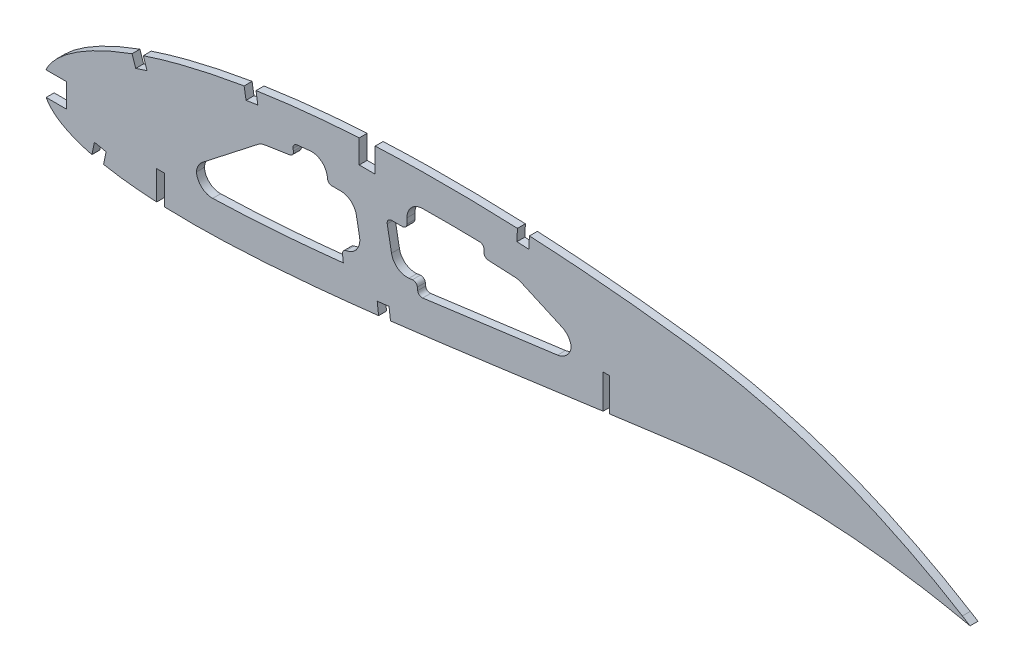
SolidWorks part; units mm, degrees
ref_plane "Front Plane" through (0, 0, 0) normal (0, 0, 1) x (1, 0, 0)
ref_plane "Top Plane" through (0, 0, 0) normal (0, 1, 0) x (1, 0, 0)
ref_plane "Right Plane" through (0, 0, 0) normal (1, 0, 0) x (0, 0, -1)
curve "Curve1"
  spline degree 3 poles (383.949, 0.5986, 0) (383.9196, 0.6168, 0) (383.802, 0.6894, 0) (383.5372, 0.8518, 0) (383.0962, 1.1224, 0) (382.4788, 1.4992, 0) (381.6856, 1.9812, 0) (380.716, 2.5651, 0) (379.5708, 3.249, 0) (378.2502, 4.0295, 0) (376.7543, 4.9032, 0) (375.0838, 5.8664, 0) (373.2387, 6.9137, 0) (371.2197, 8.0407, 0) (369.0276, 9.2423, 0) (366.6628, 10.5128, 0) (364.1261, 11.8459, 0) (361.4185, 13.2358, 0) (358.5405, 14.6749, 0) (355.4934, 16.1571, 0) (352.2782, 17.675, 0) (348.8962, 19.2207, 0) (345.3491, 20.7877, 0) (341.638, 22.3663, 0) (337.765, 23.9497, 0) (333.7318, 25.5289, 0) (329.5407, 27.0966, 0) (325.1933, 28.6428, 0) (320.6929, 30.1607, 0) (316.0417, 31.6403, 0) (311.2431, 33.0737, 0) (306.2997, 34.4516, 0) (301.2157, 35.767, 0) (295.9944, 37.0101, 0) (290.6401, 38.1728, 0) (285.1572, 39.2479, 0) (279.5502, 40.2249, 0) (273.8346, 41.1028, 0) (268.1025, 41.8331, 0) (262.3821, 42.5494, 0) (256.6703, 43.2222, 0) (250.8886, 43.8666, 0) (245.0428, 44.4788, 0) (239.1384, 45.057, 0) (233.1816, 45.5987, 0) (227.1785, 46.1022, 0) (221.135, 46.5647, 0) (215.0573, 46.9856, 0) (208.9515, 47.361, 0) (202.8242, 47.6908, 0) (196.6815, 47.9725, 0) (190.5298, 48.2044, 0) (184.3757, 48.385, 0) (178.2255, 48.5125, 0) (172.0859, 48.5861, 0) (165.9633, 48.6039, 0) (159.8643, 48.5655, 0) (153.7954, 48.4696, 0) (147.7632, 48.3149, 0) (141.7741, 48.1011, 0) (135.8345, 47.8283, 0) (129.951, 47.4942, 0) (124.1299, 47.1009, 0) (118.3778, 46.6469, 0) (112.701, 46.1319, 0) (107.1053, 45.5581, 0) (101.5971, 44.9239, 0) (96.1822, 44.2312, 0) (90.8666, 43.4813, 0) (85.6562, 42.6738, 0) (80.5566, 41.8111, 0) (75.5733, 40.894, 0) (70.7116, 39.9252, 0) (65.9768, 38.9049, 0) (61.3739, 37.8363, 0) (56.9076, 36.7211, 0) (52.5828, 35.5615, 0) (48.4038, 34.3602, 0) (44.375, 33.1199, 0) (40.5009, 31.842, 0) (36.7845, 30.5314, 0) (33.2304, 29.1889, 0) (29.8413, 27.8188, 0) (26.6212, 26.4228, 0) (23.5724, 25.0052, 0) (20.6984, 23.5677, 0) (18.0014, 22.1143, 0) (15.4839, 20.6472, 0) (13.1483, 19.1691, 0) (10.9958, 17.6837, 0) (9.0293, 16.1921, 0) (7.2493, 14.698, 0) (5.6571, 13.2036, 0) (4.255, 11.71, 0) (3.0428, 10.2198, 0) (2.0222, 8.7343, 0) (1.1933, 7.2547, 0) (0.558, 5.7822, 0) (0.1157, 4.3176, 0) (-0.1263, 2.863, 0) (-0.1866, 1.4174, 0) (-0.0621, 0.4718, 0) (0, 0, 0) knots 0 0 0 0 0.000254 0.001015 0.002283 0.004057 0.006331 0.009105 0.012374 0.016134 0.02038 0.025106 0.030306 0.035972 0.0421 0.048678 0.055702 0.06316 0.071046 0.07935 0.088063 0.097176 0.106678 0.116562 0.126814 0.137428 0.148394 0.1597 0.171338 0.183298 0.19557 0.208144 0.221012 0.234162 0.247587 0.261277 0.275223 0.289414 0.303771 0.317689 0.331784 0.34604 0.360444 0.374983 0.38964 0.404403 0.419257 0.434187 0.449177 0.464215 0.479284 0.49437 0.509458 0.524532 0.539579 0.554583 0.56953 0.584403 0.599191 0.613877 0.628447 0.642889 0.657186 0.671326 0.685294 0.699078 0.712665 0.726043 0.739198 0.752118 0.764792 0.777208 0.789356 0.801224 0.812804 0.824083 0.835055 0.84571 0.856038 0.866034 0.875689 0.884998 0.893953 0.902553 0.910789 0.918661 0.926166 0.933303 0.940071 0.946475 0.952518 0.958205 0.963547 0.968557 0.97325 0.977651 0.981787 0.985694 0.989415 0.993001 0.996508 1 1 1 1
curve "Curve2"
  spline degree 3 poles (0, 0, 0) (0.0986, -0.4654, 0) (0.2962, -1.3985, 0) (0.8332, -2.7416, 0) (1.5434, -4.0328, 0) (2.4415, -5.2686, 0) (3.5218, -6.4485, 0) (4.7818, -7.574, 0) (6.2202, -8.6443, 0) (7.8352, -9.659, 0) (9.6244, -10.6191, 0) (11.5859, -11.5241, 0) (13.7178, -12.3737, 0) (16.0178, -13.1667, 0) (18.4831, -13.9043, 0) (21.1113, -14.5848, 0) (23.8995, -15.2091, 0) (26.845, -15.7756, 0) (29.9446, -16.2848, 0) (33.195, -16.7366, 0) (36.593, -17.1311, 0) (40.1351, -17.4676, 0) (43.8179, -17.7467, 0) (47.6377, -17.9687, 0) (51.5909, -18.1343, 0) (55.6735, -18.2428, 0) (59.8817, -18.2959, 0) (64.2115, -18.2945, 0) (68.6589, -18.238, 0) (73.2199, -18.1297, 0) (77.8902, -17.9689, 0) (82.6657, -17.7575, 0) (87.5419, -17.4976, 0) (92.5144, -17.1902, 0) (97.5791, -16.8365, 0) (102.7313, -16.4394, 0) (107.9665, -16, 0) (113.2801, -15.5207, 0) (118.6674, -15.0039, 0) (124.1237, -14.4514, 0) (129.6442, -13.8657, 0) (135.2241, -13.2487, 0) (140.8584, -12.6036, 0) (146.5422, -11.9317, 0) (152.2705, -11.2369, 0) (158.0381, -10.5203, 0) (163.84, -9.7848, 0) (169.6711, -9.0339, 0) (175.5259, -8.2674, 0) (181.3995, -7.4908, 0) (187.2862, -6.7036, 0) (193.1809, -5.9096, 0) (199.0781, -5.1115, 0) (204.9721, -4.3094, 0) (210.8578, -3.5066, 0) (216.7295, -2.7054, 0) (222.5817, -1.9059, 0) (228.409, -1.112, 0) (234.2055, -0.3236, 0) (239.9659, 0.4577, 0) (245.6847, 1.2295, 0) (251.3565, 1.9909, 0) (256.9754, 2.7413, 0) (262.5357, 3.4812, 0) (267.9487, 4.188, 0) (273.2002, 4.8993, 0) (278.3079, 5.4825, 0) (283.3519, 5.9802, 0) (288.3377, 6.3883, 0) (293.259, 6.7125, 0) (298.1104, 6.9553, 0) (302.886, 7.1201, 0) (307.5799, 7.2116, 0) (312.186, 7.2323, 0) (316.6983, 7.1886, 0) (321.1107, 7.0842, 0) (325.4171, 6.9238, 0) (329.6115, 6.7126, 0) (333.688, 6.4566, 0) (337.6405, 6.1594, 0) (341.4634, 5.828, 0) (345.1508, 5.4673, 0) (348.6971, 5.0813, 0) (352.0971, 4.6782, 0) (355.3453, 4.2606, 0) (358.4369, 3.8354, 0) (361.3669, 3.4069, 0) (364.1307, 2.9806, 0) (366.7239, 2.5605, 0) (369.1422, 2.1521, 0) (371.3821, 1.7594, 0) (373.4394, 1.3862, 0) (375.3115, 1.0371, 0) (376.9946, 0.7139, 0) (378.4864, 0.4219, 0) (379.7842, 0.1625, 0) (380.886, -0.0608, 0) (381.79, -0.247, 0) (382.4947, -0.3932, 0) (382.9989, -0.4995, 0) (383.3019, -0.5627, 0) (383.4365, -0.5914, 0) (383.4701, -0.5986, 0) knots 0 0 0 0 0.003638 0.007293 0.011028 0.014901 0.018963 0.023258 0.027821 0.032679 0.037853 0.043362 0.049215 0.055422 0.061989 0.068918 0.076211 0.083868 0.091887 0.100266 0.109 0.118085 0.127515 0.137285 0.147388 0.157816 0.168563 0.179619 0.190977 0.202627 0.21456 0.226767 0.239236 0.251959 0.264924 0.27812 0.291536 0.30516 0.318981 0.332985 0.347163 0.361499 0.375981 0.390597 0.405333 0.420175 0.43511 0.450124 0.465203 0.480333 0.495501 0.51069 0.525887 0.541078 0.556247 0.571382 0.586466 0.601485 0.616424 0.631269 0.646007 0.660621 0.675098 0.689423 0.703582 0.716908 0.730009 0.742952 0.755726 0.76832 0.780724 0.792927 0.804916 0.816679 0.828204 0.839475 0.850481 0.861208 0.871639 0.881763 0.891564 0.901027 0.910139 0.918884 0.927249 0.935221 0.942785 0.949928 0.956638 0.962904 0.968712 0.974054 0.978918 0.983297 0.98718 0.990561 0.993433 0.995791 0.99763 0.998946 0.999737 1 1 1 1
sketch "Sketch1" plane through (0, 0, 0) normal (0, 0, 1) x (1, 0, 0)
  line L23 (366.7792, -0.5725) -> (370.31, -1.3257)
  line L24 (367.2372, 0.5725) -> (370.31, -1.3257)
  spline S4 degree 3 poles (0, 0) (0.0943, -0.4452) (0.2833, -1.3376) (0.797, -2.6223) (1.4762, -3.8573) (2.3353, -5.0392) (3.3685, -6.1679) (4.5736, -7.2443) (5.9495, -8.2681) (7.4942, -9.2386) (9.2055, -10.1569) (11.0816, -11.0225) (13.1207, -11.8351) (15.3206, -12.5936) (17.6786, -13.2991) (20.1924, -13.95) (22.8593, -14.5471) (25.6766, -15.0889) (28.6412, -15.576) (31.7502, -16.0081) (35.0002, -16.3855) (38.3882, -16.7073) (41.9107, -16.9743) (45.5643, -17.1866) (49.3453, -17.345) (53.2503, -17.4488) (57.2753, -17.4996) (61.4167, -17.4982) (65.6704, -17.4442) (70.0329, -17.3406) (74.5, -17.1868) (79.0676, -16.9846) (83.7315, -16.736) (88.4877, -16.442) (93.3319, -16.1037) (98.2599, -15.7239) (103.2672, -15.3035) (108.3495, -14.8451) (113.5023, -14.3509) (118.7211, -13.8224) (124.0014, -13.2622) (129.3383, -12.672) (134.7274, -12.055) (140.1638, -11.4124) (145.6428, -10.7478) (151.1593, -10.0624) (156.7087, -9.3589) (162.286, -8.6407) (167.886, -7.9075) (173.5039, -7.1648) (179.1344, -6.4118) (184.7725, -5.6524) (190.4131, -4.889) (196.0505, -4.1218) (201.68, -3.354) (207.2962, -2.5877) (212.8937, -1.823) (218.4673, -1.0636) (224.0115, -0.3095) (229.5212, 0.4377) (234.9911, 1.176) (240.416, 1.9042) (245.7903, 2.622) (251.1086, 3.3297) (256.286, 4.0057) (261.3089, 4.6861) (266.1943, 5.2438) (271.0188, 5.7199) (275.7875, 6.1102) (280.4947, 6.4204) (285.1349, 6.6526) (289.7027, 6.8102) (294.1922, 6.8977) (298.5979, 6.9175) (302.9137, 6.8757) (307.134, 6.7759) (311.253, 6.6224) (315.2649, 6.4204) (319.164, 6.1755) (322.9444, 5.8913) (326.6009, 5.5743) (330.1278, 5.2293) (333.5197, 4.8601) (336.7717, 4.4746) (339.8786, 4.0752) (342.8356, 3.6685) (345.6381, 3.2586) (348.2816, 2.8509) (350.7619, 2.449) (353.075, 2.0585) (355.2173, 1.6829) (357.1852, 1.3259) (358.9757, 0.992) (360.5855, 0.6828) (362.0124, 0.4036) (363.2537, 0.1554) (364.3076, -0.0582) (365.1722, -0.2363) (365.8463, -0.3761) (366.3285, -0.4777) (366.6183, -0.5382) (366.7471, -0.5657) (366.7792, -0.5725) knots 0 0 0 0 0.003638 0.007293 0.011028 0.014901 0.018963 0.023258 0.027821 0.032679 0.037853 0.043362 0.049215 0.055422 0.061989 0.068918 0.076211 0.083868 0.091887 0.100266 0.109 0.118085 0.127515 0.137285 0.147388 0.157816 0.168563 0.179619 0.190977 0.202627 0.21456 0.226767 0.239236 0.251959 0.264924 0.27812 0.291536 0.30516 0.318981 0.332985 0.347163 0.361499 0.375981 0.390597 0.405333 0.420175 0.43511 0.450124 0.465203 0.480333 0.495501 0.51069 0.525887 0.541078 0.556247 0.571382 0.586466 0.601485 0.616424 0.631269 0.646007 0.660621 0.675098 0.689423 0.703582 0.716908 0.730009 0.742952 0.755726 0.76832 0.780724 0.792927 0.804916 0.816679 0.828204 0.839475 0.850481 0.861208 0.871639 0.881763 0.891564 0.901027 0.910139 0.918884 0.927249 0.935221 0.942785 0.949928 0.956638 0.962904 0.968712 0.974054 0.978918 0.983297 0.98718 0.990561 0.993433 0.995791 0.99763 0.998946 0.999737 1 1 1 1
  spline S5 degree 3 poles (367.2372, 0.5725) (367.2091, 0.5899) (367.0967, 0.6594) (366.8434, 0.8147) (366.4216, 1.0735) (365.8311, 1.4339) (365.0724, 1.895) (364.145, 2.4534) (363.0497, 3.1075) (361.7865, 3.8541) (360.3558, 4.6898) (358.7579, 5.6111) (356.9931, 6.6127) (355.062, 7.6908) (352.9654, 8.84) (350.7035, 10.0552) (348.2772, 11.3303) (345.6874, 12.6597) (342.9347, 14.0361) (340.0202, 15.4538) (336.945, 16.9057) (333.7102, 18.3841) (330.3175, 19.8829) (326.7679, 21.3928) (323.0635, 22.9073) (319.2058, 24.4177) (315.1971, 25.9172) (311.039, 27.3961) (306.7345, 28.8479) (302.2857, 30.2631) (297.6959, 31.6342) (292.9677, 32.9521) (288.105, 34.2102) (283.111, 35.3992) (277.9897, 36.5112) (272.7455, 37.5396) (267.3825, 38.474) (261.9157, 39.3138) (256.4331, 40.0123) (250.9617, 40.6974) (245.4985, 41.341) (239.9685, 41.9573) (234.3771, 42.5429) (228.7297, 43.0959) (223.0322, 43.6139) (217.2904, 44.0955) (211.5099, 44.5379) (205.6967, 44.9405) (199.8567, 45.2996) (193.9961, 45.615) (188.1207, 45.8845) (182.2368, 46.1063) (176.3505, 46.279) (170.468, 46.4009) (164.5957, 46.4714) (158.7396, 46.4884) (152.9061, 46.4516) (147.1013, 46.3599) (141.3317, 46.212) (135.6032, 46.0075) (129.9222, 45.7465) (124.2948, 45.427) (118.7271, 45.0508) (113.2253, 44.6165) (107.7956, 44.1239) (102.4435, 43.5751) (97.175, 42.9685) (91.9958, 42.306) (86.9116, 41.5888) (81.9279, 40.8164) (77.0503, 39.9912) (72.2839, 39.114) (67.6338, 38.1874) (63.1051, 37.2115) (58.7025, 36.1894) (54.4306, 35.1228) (50.2941, 34.0137) (46.297, 32.8646) (42.4435, 31.6784) (38.7381, 30.4561) (35.1834, 29.2025) (31.784, 27.9184) (28.5424, 26.6079) (25.4625, 25.2727) (22.5464, 23.9168) (19.7975, 22.5419) (17.2178, 21.1517) (14.8099, 19.7485) (12.5761, 18.3347) (10.5172, 16.914) (8.6363, 15.4873) (6.9338, 14.0582) (5.4109, 12.6289) (4.0698, 11.2003) (2.9103, 9.775) (1.9341, 8.3541) (1.1413, 6.9389) (0.5337, 5.5305) (0.1107, 4.1296) (-0.1208, 2.7384) (-0.1785, 1.3557) (-0.0594, 0.4512) (0, 0) knots 0 0 0 0 0.000254 0.001015 0.002283 0.004057 0.006331 0.009105 0.012374 0.016134 0.02038 0.025106 0.030306 0.035972 0.0421 0.048678 0.055702 0.06316 0.071046 0.07935 0.088063 0.097176 0.106678 0.116562 0.126814 0.137428 0.148394 0.1597 0.171338 0.183298 0.19557 0.208144 0.221012 0.234162 0.247587 0.261277 0.275223 0.289414 0.303771 0.317689 0.331784 0.34604 0.360444 0.374983 0.38964 0.404403 0.419257 0.434187 0.449177 0.464215 0.479284 0.49437 0.509458 0.524532 0.539579 0.554583 0.56953 0.584403 0.599191 0.613877 0.628447 0.642889 0.657186 0.671326 0.685294 0.699078 0.712665 0.726043 0.739198 0.752118 0.764792 0.777208 0.789356 0.801224 0.812804 0.824083 0.835055 0.84571 0.856038 0.866034 0.875689 0.884998 0.893953 0.902553 0.910789 0.918661 0.926166 0.933303 0.940071 0.946475 0.952518 0.958205 0.963547 0.968557 0.97325 0.977651 0.981787 0.985694 0.989415 0.993001 0.996508 1 1 1 1
extrude "Boss-Extrude1" add sketch "Sketch1" along normal blind 3.175
sketch "Sketch2" plane through (0, 0, 0) normal (0, 0, -1) x (-1, 0, 0)
  line L0 (-226.1759, 13.2245) -> (-223.6359, 13.2245)
  line L1 (-226.1759, 0.0342) -> (-226.1759, -1.6012)
  line L2 (-48.3759, -5.601) -> (-48.3759, -17.018)
  line L4 (-226.1759, -1.6012) -> (-223.6359, -0.7835)
  line L5 (-223.6359, -0.7835) -> (-223.6359, 0.0342)
  line L7 (-132.5134, 45.7369) -> (-132.5134, 36.144)
  line L8 (-132.5134, 36.144) -> (-126.1634, 36.144)
  line L9 (-132.5134, 45.7369) -> (-132.5134, 48.5008)
  line L10 (-226.1759, 13.2245) -> (-226.1759, 0.0342)
  line L12 (-132.5134, 48.5008) -> (-126.1634, 46.56)
  line L13 (-126.1634, 46.56) -> (-126.1634, 45.7369)
  line L14 (-45.2009, -5.601) -> (-45.2009, -17.018)
  line L16 (-48.3759, -5.601) -> (-45.2009, -5.601)
  line L17 (-48.3759, -17.018) -> (-48.3759, -19.7506)
  line L19 (-126.1634, 45.7369) -> (-126.1634, 36.144)
  line L20 (-48.3759, -19.7506) -> (-45.2009, -18.0441)
  line L21 (-45.2009, -18.0441) -> (-45.2009, -17.018)
  line L22 (-223.6359, 13.2245) -> (-223.6359, 0.0342)
extrude "Cut-Extrude1" cut sketch "Sketch2" against normal blind 7.62
sketch "Sketch3" plane through (0, 0, 3.175) normal (0, 0, 1) x (1, 0, 0)
  line L1 (-0.4139, 6.4879) -> (9.1111, 6.4879)
  line L2 (133.8957, -12.1377) -> (134.1695, -14.4701)
  line L3 (9.1111, -3.0371) -> (9.1111, 6.4879)
  line L4 (138.6396, -11.5807) -> (138.9134, -13.9131)
  line L5 (24.9672, -9.877) -> (20.307, -8.9078)
  line L6 (134.1695, -14.4701) -> (138.9134, -13.9131)
  line L7 (23.9692, -14.6694) -> (24.9672, -9.877)
  line L9 (41.3214, 26.3939) -> (39.8106, 30.9067)
  line L11 (85.6243, 36.6261) -> (84.9023, 41.3353)
  line L13 (138.0771, -6.8447) -> (133.3478, -7.4064)
  line L15 (138.6396, -11.5807) -> (138.0771, -6.8447)
  line L17 (193.9411, 40.8593) -> (194.1833, 45.6146)
  line L19 (-0.4139, -3.0371) -> (-0.4139, 6.4879)
  line L21 (-0.4139, -3.0371) -> (9.1111, -3.0371)
  line L23 (20.307, -8.9078) -> (19.3375, -13.5718)
  line L25 (80.1398, 40.5723) -> (80.9168, 35.9044)
  line L27 (80.9168, 35.9044) -> (85.6243, 36.6261)
  line L29 (133.3478, -7.4064) -> (133.8957, -12.1377)
  line L31 (189.3949, 45.8428) -> (189.1847, 41.0997)
  line L33 (189.1847, 41.0997) -> (193.9411, 40.8593)
  line L35 (35.312, 29.3422) -> (36.8054, 24.882)
  line L37 (36.8054, 24.882) -> (41.3214, 26.3939)
  line L39 (19.3375, -13.5718) -> (19.0177, -14.9208)
  line L40 (23.9692, -14.6694) -> (23.6495, -16.0185)
  line L41 (19.0177, -14.9208) -> (23.6495, -16.0185)
  arc A1 (194.1833, 45.6146) -> (189.3949, 45.8428) centre (155.1187, -723.9718) ccw
  spline S1 degree 3 poles (39.8106, 30.9067) (39.3989, 30.7692) (37.8946, 30.2613) (36.3966, 29.7352) (35.312, 29.3422) knots 0 0 0 0 0.273428 1 1 1 1
  spline S3 degree 3 poles (84.9023, 41.3353) (83.9797, 41.1935) (82.3915, 40.9435) (80.8049, 40.6833) (80.1398, 40.5723) knots 0 0 0 0 0.580571 1 1 1 1
extrude "Cut-Extrude2" cut sketch "Sketch3" against normal blind 7.62
sketch "Sketch4" plane through (0, 0, 3.175) normal (0, 0, 1) x (1, 0, 0)
  line L0 (124.0505, 23.444) -> (119.8134, 23.444)
  line L1 (61.0759, 3.8422) -> (61.0759, -4.7919)
  line L2 (119.8135, -0.9342) -> (119.2755, 3.7114)
  line L3 (119.2755, 3.7114) -> (127.5024, 4.6885)
  line L4 (140.1395, 6.1895) -> (149.1905, 7.2645)
  line L5 (210.9359, 18.8713) -> (189.752, 28.3548)
  line L6 (113.4634, 23.444) -> (113.4634, 31.88)
  line L7 (99.4216, 30.4365) -> (100.1022, 25.9974)
  line L8 (100.1022, 25.9974) -> (86.8727, 23.9691)
  line L9 (61.0759, 3.8422) -> (86.8727, 23.9691)
  line L10 (210.9359, 25.8286) -> (210.9359, 25.9245)
  line L12 (189.752, 28.3548) -> (175.9385, 29.0531)
  line L13 (124.0505, 23.444) -> (113.4634, 23.444)
  line L15 (127.5024, 4.6885) -> (124.0505, 23.444)
  line L16 (175.9385, 29.0531) -> (176.1387, 33.5719)
  line L17 (145.2134, 33.6045) -> (145.2134, 23.444)
  line L18 (145.2134, 23.444) -> (136.9638, 23.444)
  line L19 (125.5627, 4.4581) -> (127.5024, 4.6885)
  line L20 (149.1905, 7.2645) -> (149.749, 2.5622)
  line L21 (210.9359, 10.7271) -> (210.9359, 18.8713)
  line L23 (140.1395, 6.1895) -> (136.9638, 23.444)
  line L33 (46.7884, 0.749) -> (84.2728, 29.9947) construction
  line L34 (224.9059, 19.5745) -> (191.2608, 34.6367) construction
  line L35 (134.9727, -0.8188) -> (129.3384, 29.794) construction
  line L90 (15.4611, 12.6036) -> (15.4611, -1.4142) construction
  line L91 (15.4611, -1.4142) -> (32.4788, -4.9532) construction
  line L92 (32.4788, -4.9532) -> (31.5192, -9.5611) construction
  line L93 (38.8509, -10.3626) -> (38.8509, 0.749) construction
  line L94 (38.8509, 0.749) -> (54.7259, 0.749) construction
  line L95 (54.7259, 0.749) -> (54.7259, -11.1139) construction
  line L96 (126.857, -6.5565) -> (126.3117, -1.8475) construction
  line L97 (126.3117, -1.8475) -> (143.6338, 0.2099) construction
  line L98 (143.6338, 0.2099) -> (144.1962, -4.5249) construction
  line L99 (217.2859, 5.1839) -> (217.2859, 19.5745) construction
  line L100 (217.2859, 19.5745) -> (232.5259, 19.5745) construction
  line L101 (232.5259, 19.5745) -> (232.5259, 7.2506) construction
  line L102 (200.2001, 38.9114) -> (199.9599, 34.1969) construction
  line L103 (199.9599, 34.1969) -> (182.5616, 35.0764) construction
  line L104 (182.5616, 35.0764) -> (182.7677, 39.7263) construction
  line L105 (138.8634, 39.7674) -> (138.8634, 29.794) construction
  line L106 (138.8634, 29.794) -> (119.8134, 29.794) construction
  line L107 (119.8134, 29.794) -> (119.8134, 38.7525) construction
  line L108 (92.1584, 35.9089) -> (92.8632, 31.3117) construction
  line L109 (92.8632, 31.3117) -> (75.6823, 28.6777) construction
  line L110 (75.6823, 28.6777) -> (74.9393, 33.1419) construction
  line L111 (47.9131, 26.7069) -> (49.3588, 22.3884) construction
  line L112 (49.3588, 22.3884) -> (32.7999, 16.8445) construction
  line L113 (32.7999, 16.8445) -> (31.4358, 20.9189) construction
  spline S1 degree 3 poles (61.0759, -4.7919) (65.956, -4.7644) (75.6976, -4.4951) (90.3945, -3.6335) (105.0964, -2.4282) (114.9126, -1.4532) (119.8135, -0.9342) knots 0.088297 0.088297 0.088297 0.088297 0.294057 0.499818 0.705579 0.911339 0.911339 0.911339 0.911339
  spline S3 degree 3 poles (113.4634, 31.88) (112.2906, 31.7785) (109.9455, 31.5663) (106.4329, 31.2203) (102.9244, 30.8456) (100.5889, 30.5762) (99.4216, 30.4365) knots 0.248835 0.248835 0.248835 0.248835 0.377634 0.506434 0.635234 0.764034 0.764034 0.764034 0.764034
  spline S5 degree 3 poles (176.1387, 33.5719) (173.5606, 33.6369) (168.4029, 33.7373) (160.6696, 33.7956) (152.938, 33.7586) (147.7883, 33.6675) (145.2134, 33.6045) knots 0.147373 0.147373 0.147373 0.147373 0.325248 0.503123 0.680998 0.858873 0.858873 0.858873 0.858873
  spline S7 degree 3 poles (149.749, 2.5622) (154.8468, 3.2019) (165.0342, 4.5157) (180.3292, 6.5582) (195.6275, 8.6359) (205.8337, 10.0311) (210.9359, 10.7271) knots 0.086693 0.086693 0.086693 0.086693 0.296227 0.505762 0.715296 0.924831 0.924831 0.924831 0.924831
  spline S29 degree 3 poles (31.4358, 20.9189) (28.6531, 19.7653) (25.916, 18.5237) (21.9074, 16.4737) (20.5873, 15.759) (17.9891, 14.2488) (16.7091, 13.4524) (15.4611, 12.6036) knots 0 0 0 0 0.5 0.5 0.75 0.75 1 1 1 1 construction
  spline S30 degree 3 poles (31.5192, -9.5611) (33.9561, -9.8911) (36.4008, -10.1525) (38.8509, -10.3626) knots 0 0 0 0 1 1 1 1 construction
  spline S31 degree 3 poles (54.7259, -11.1139) (60.7538, -11.2031) (66.7785, -11.1065) (78.8236, -10.6715) (84.8424, -10.3327) (96.8659, -9.4865) (102.8724, -8.9793) (114.8725, -7.8476) (120.8667, -7.2227) (126.857, -6.5565) knots 0 0 0 0 0.25 0.25 0.5 0.5 0.75 0.75 1 1 1 1 construction
  spline S32 degree 3 poles (144.1962, -4.5249) (156.3939, -3.0317) (168.5773, -1.4251) (192.9351, 1.8535) (205.1095, 3.5262) (217.2859, 5.1839) knots 0 0 0 0 0.5 0.5 1 1 1 1 construction
  spline S33 degree 3 poles (232.5259, 7.2506) (236.7454, 7.8194) (240.9653, 8.3846) (247.2957, 9.2284) (249.406, 9.5085) (252.572, 9.9246) (253.6273, 10.0631) (255.7377, 10.3424) (256.7926, 10.4843) (258.903, 10.7638) (259.9585, 10.901) (262.0714, 11.1604) (263.1287, 11.2834) (266.3027, 11.6351) (268.4217, 11.8485) (274.7855, 12.4209) (279.0307, 12.7117) (287.5261, 13.1156) (291.7763, 13.2287) (300.2819, 13.2775) (304.5386, 13.2148) (317.3074, 12.7665) (325.7774, 12.1249) (334.2082, 11.1674) knots 0 0 0 0 0.125 0.125 0.1875 0.1875 0.21875 0.21875 0.25 0.25 0.28125 0.28125 0.3125 0.3125 0.375 0.375 0.5 0.5 0.625 0.625 0.75 0.75 1 1 1 1 construction
  spline S34 degree 3 poles (334.2082, 11.1674) (331.593, 12.3814) (328.9576, 13.5555) (323.6447, 15.8208) (320.9638, 16.9136) (312.8924, 20.0522) (307.47, 21.9608) (291.0773, 27.1309) (279.9822, 29.8393) (265.8998, 32.2791) (263.0735, 32.7235) (258.8151, 33.3063) (257.3929, 33.4883) (254.5475, 33.8483) (253.1245, 34.0271) (246.0062, 34.9053) (240.2966, 35.5479) (223.1381, 37.304) (211.6798, 38.2388) (200.2001, 38.9114) knots 0 0 0 0 0.0625 0.0625 0.125 0.125 0.25 0.25 0.5 0.5 0.5625 0.5625 0.59375 0.59375 0.625 0.625 0.75 0.75 1 1 1 1 construction
  spline S35 degree 3 poles (182.7677, 39.7263) (175.4529, 39.9792) (168.1344, 40.1179) (153.497, 40.1411) (146.178, 40.0263) (138.8634, 39.7674) knots 0 0 0 0 0.5 0.5 1 1 1 1 construction
  spline S36 degree 3 poles (119.8134, 38.7525) (110.5679, 38.0873) (101.3431, 37.1604) (92.1584, 35.9089) knots 0 0 0 0 1 1 1 1 construction
  spline S37 degree 3 poles (74.9393, 33.1419) (70.3845, 32.2908) (65.8479, 31.3424) (56.8317, 29.213) (52.3534, 28.033) (47.9131, 26.7069) knots 0 0 0 0 0.5 0.5 1 1 1 1 construction
extrude "Cut-Extrude3" cut sketch "Sketch4" against normal blind 7.62 contours L6 S3 L7 L8 L9 L1 S1 L2 L3 L15 L0 L13 | L20 S7 L21 L5 L12 L16 S5 L17 L18 L23 L4 region at (96.5424, 10.5191, 3.175) region at (170.5642, 18.1833, 3.175)
fillet "Fillet1" radius 6.35 11 edges at (210.9359, 10.7271, 1.5875) (210.9359, 18.8713, 1.5875) (189.752, 28.3548, 1.5875) (140.1395, 6.1895, 1.5875) (145.2134, 33.6045, 1.5875) (113.4634, 31.88, 1.5875) (124.0505, 23.444, 1.5875) (127.5024, 4.6885, 1.5875) (86.8727, 23.9691, 1.5875) (61.0759, 3.8422, 1.5875) (61.0759, -4.7919, 1.5875)
fillet "Fillet2" radius 1.778 10 edges at (175.9385, 29.0531, 1.5875) (176.1387, 33.5719, 1.5875) (145.2134, 23.444, 1.5875) (136.9638, 23.444, 1.5875) (149.749, 2.5622, 1.5875) (149.1905, 7.2645, 1.5875) (119.2755, 3.7114, 1.5875) (113.4634, 23.444, 1.5875) (99.4216, 30.4365, 1.5875) (100.1022, 25.9974, 1.5875)
